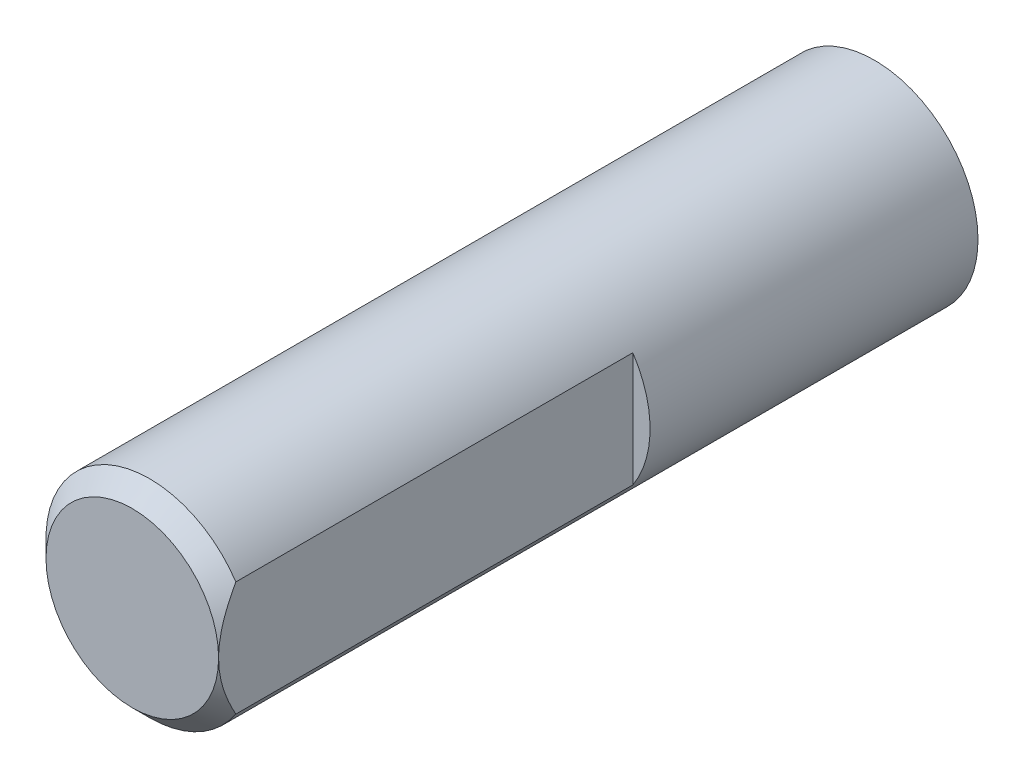
SolidWorks part; units mm, degrees
material "Alloy Steel"
ref_plane "Front Plane" through (0, 0, 0) normal (0, 0, 1) x (1, 0, 0)
ref_plane "Top Plane" through (0, 0, 0) normal (0, 1, 0) x (1, 0, 0)
ref_plane "Right Plane" through (0, 0, 0) normal (1, 0, 0) x (0, 0, -1)
sketch "Sketch1" plane through (0, 0, 0) normal (0, 0, 1) x (1, 0, 0)
  circle A0 centre (0, 0) radius 3
  dimension "D1" = 6
extrude "Boss-Extrude1" add sketch "Sketch1" along normal blind 21.5
sketch "Sketch2" plane through (0, 0, 21.5) normal (0, 0, 1) x (1, 0, 0)
  line L0 (2.5, 1.6583) -> (2.5, -1.6583)
  line L1 (0, 0) -> (2.5, 0) construction
  line L2 (2.5, 0) -> (3, 0) construction
  circle A1 centre (0, 0) radius 3
  arc A2 (2.5, -1.6583) -> (2.5, 1.6583) centre (0, 0) ccw
  dimension "D2" = 0.5
  dimension "D1" = 0
extrude "Cut-Extrude1" cut sketch "Sketch2" against normal blind 12
chamfer "Chamfer1" distance 0.5 angle 45 1 edges at (-3, 0, 21.5)
